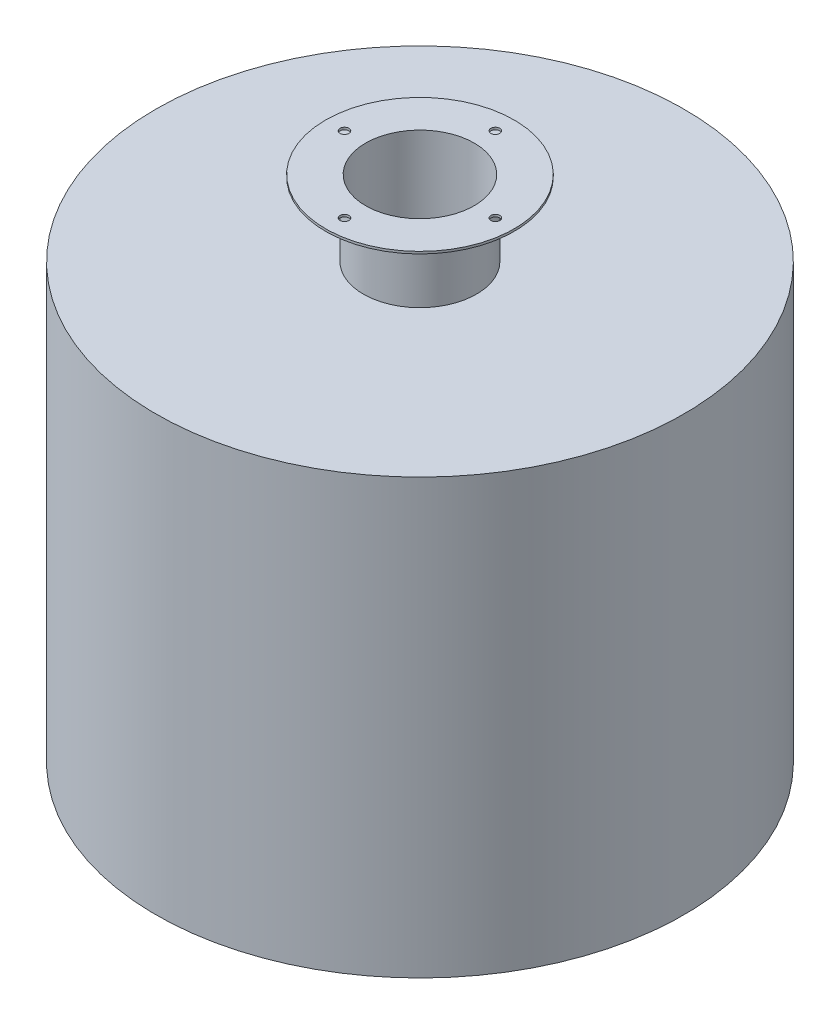
SolidWorks part; units mm, degrees
material "201 Annealed Stainless Steel (SS)"
ref_plane "Front Plane" through (0, 0, 0) normal (0, 0, 1) x (1, 0, 0)
ref_plane "Top Plane" through (0, 0, 0) normal (0, 1, 0) x (1, 0, 0)
ref_plane "Right Plane" through (0, 0, 0) normal (1, 0, 0) x (0, 0, -1)
sketch "Sketch1" plane through (0, 0, 0) normal (0, 0, 1) x (1, 0, 0)
  line L0 (0, 0) -> (177.8, 0)
  line L1 (177.8, 0) -> (177.8, 292.1)
  line L2 (177.8, 292.1) -> (38.1, 292.1)
  line L3 (38.1, 292.1) -> (38.1, 341.376)
  line L4 (38.1, 341.376) -> (63.5, 341.376)
  line L5 (63.5, 341.376) -> (63.5, 342.9)
  line L6 (63.5, 342.9) -> (0, 342.9)
  line L7 (0, 342.9) -> (0, 0)
  dimension "D1" = 177.8
  dimension "D2" = 342.9
  dimension "D3" = 1.524
  dimension "D4" = 292.1
  dimension "D6" = 63.5
  dimension "D7" = 38.1
revolve "Revolve1" add sketch "Sketch1" angle 360 about L7
shell "Shell2" thickness 1.524 removed face at (-63.5, 342.9, 0)
sketch "Sketch2" plane through (0, 342.9, 0) normal (0, 1, 0) x (1, 0, 0)
  circle A0 centre (50.8, 0) radius 3
  dimension "D1" = 6
  dimension "D2" = 50.8
extrude "Cut-Extrude1" cut sketch "Sketch2" against normal up to next
pattern_circular "CirPattern1" count 4 over 360 about axis through (0, 342.9, 0) along (0, 1, 0) of "Cut-Extrude1"
